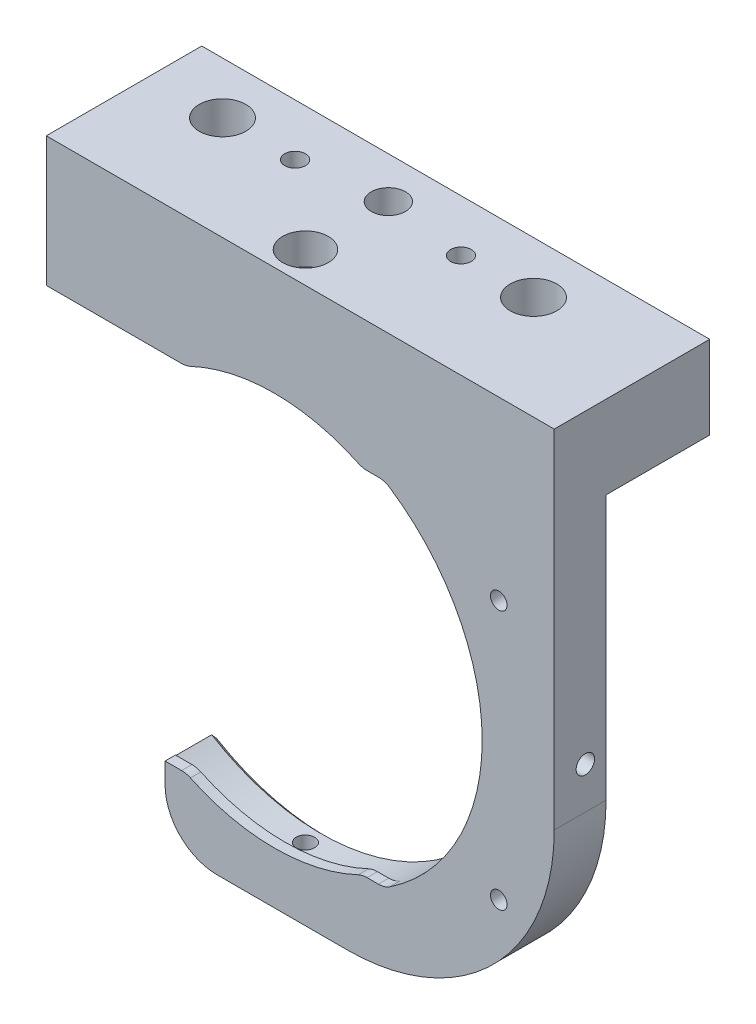
SolidWorks part; units mm, degrees
material "6061 合金"
ref_plane "前视基准面" through (0, 0, 0) normal (0, 0, 1) x (1, 0, 0)
ref_plane "上视基准面" through (0, 0, 0) normal (0, 1, 0) x (1, 0, 0)
ref_plane "右视基准面" through (0, 0, 0) normal (1, 0, 0) x (0, 0, -1)
sketch "草图2" plane through (0, 0, 0) normal (0, 0, 1) x (1, 0, 0)
  circle A0 centre (0, 0) radius 22
extrude "凸台-拉伸1" add sketch "草图2" along normal blind 5
sketch "草图4" plane through (0, 0, 0) normal (0, 0, -1) x (-1, 0, 0)
  line L0 (0, 22) -> (0, -22) construction
  line L1 (-23.9655, 0) -> (23.9655, 0) construction
  circle A0 centre (0, 0) radius 22 construction
  circle A1 centre (0, 0) radius 5.1407
  point P10 (0, 0)
sketch "草图5" plane through (0, 0, 5) normal (0, 0, 1) x (1, 0, 0)
  line L5 (-3.5, 29.5) -> (3.5, 29.5)
  line L6 (-3.5, 29.5) -> (-3.5, 14.5)
  line L13 (-3.5, 14.5) -> (3.5, 14.5)
  line L14 (3.5, 29.5) -> (3.5, 14.5)
  line L15 (-3.5, 29.5) -> (3.5, 14.5) construction
  line L16 (-3.5, 14.5) -> (3.5, 29.5) construction
  point P1 (0, 22)
  dimension "D1" = 15
  dimension "D2" = 7
extrude "凸台-拉伸2" add sketch "草图5" against normal up to surface (5 mm away) up to face at (22, 0, 0)
ref_plane "基准面4" through (-22, 0, 0) normal (-1, 0, 0) x (0, 0, 1)
sketch "草图3" plane through (0, 0, 5) normal (0, 0, 1) x (1, 0, 0)
  circle A0 centre (0, 0) radius 20.05
extrude "切除-拉伸1" [suppressed] cut sketch "草图3" against normal blind 4
sketch "草图6" plane through (-22, 0, 0) normal (-1, 0, 0) x (0, 0, 1)
  line L0 (5, -0.1401) -> (2, -0.1401) construction
  line L1 (5, -22) -> (5, 21.7198) construction
  dimension "D1" = 3
sketch "草图10" plane through (0, 29.5, 0) normal (0, 1, 0) x (1, 0, 0)
  line L0 (-3.5, -2) -> (3.5, -2) construction
  line L1 (-3.5, -5) -> (-3.5, 0) construction
  line L2 (3.5, 0) -> (3.5, -5) construction
  line L3 (0, -2) -> (0, -5) construction
  dimension "D1" = 3
hole_wizard "#2-56 螺纹孔3" positions "3D草图4" profile "草图12" tap size "#2-56" standard "ANSI Inch"
sketch3d "3D草图4"
  point P0 (0, 29.5, 2)
cosmetic thread "孔螺蚊线2" parameters "D1"=4.37, "D2"=2.1844
sketch "草图12" plane through (0, 29.5, 2) normal (1, 0, 0) x (0, 0, 1)
  line L0 (0, 0) -> (0, 15.5342)
  line L1 (0, 15.5342) -> (0.889, 15)
  line L2 (0.889, 15) -> (0.889, 0)
  line L5 (0.889, 0) -> (0, 0)
  line L10 (0, 15.5342) -> (-0.889, 15) construction
  line L11 (0, -6.35) -> (0, 107.95) construction
  dimension "螺纹孔钻头直径" = 1.778
  dimension "螺纹孔钻头深度" = 15
  dimension "导头角度" = 118
sketch "草图13" plane through (0, 0, 0) normal (0, 0, -1) x (-1, 0, 0)
  circle A0 centre (0, 0) radius 20.05
extrude "切除-拉伸2" cut sketch "草图13" against normal offset from surface (4 mm away) 1 up to face at (0, 14.68, 5)
sketch "草图14" plane through (0, 0, 4) normal (0, 0, -1) x (-1, 0, 0)
  circle A0 centre (0, 0) radius 19
extrude "切除-拉伸3" cut sketch "草图14" against normal blind 2
sketch "草图15" plane through (0, 0, 4) normal (0, 0, -1) x (-1, 0, 0)
  line L0 (-10.6303, 17) -> (10.6303, 17)
  line L1 (-10.6303, -17) -> (10.6303, -17)
  line L3 (-23.9655, 0) -> (23.9655, 0) construction
  circle A0 centre (0, 0) radius 20.05 construction
  arc A1 (-10.6303, 17) -> (-10.6303, -17) centre (0, 0) ccw
  arc A2 (10.6303, -17) -> (10.6303, 17) centre (0, 0) ccw
  dimension "D1" = 17
  dimension "D2" = 17
extrude "切除-拉伸4" cut sketch "草图15" against normal through all
sketch "草图16" plane through (0, 29.5, 0) normal (0, 1, 0) x (1, 0, 0)
  line L0 (-22, -5) -> (-22, -2) construction
  line L1 (-3.5, 0) -> (-22, 0)
  line L2 (-3.5, 0) -> (-3.5, -5)
  line L3 (-3.5, -5) -> (-22, -5)
  line L4 (-22, 0) -> (-22, -5)
  line L6 (3.5, 0) -> (22, 0)
  line L7 (3.5, 0) -> (3.5, -5)
  line L8 (3.5, -5) -> (22, -5)
  line L9 (22, 0) -> (22, -5)
extrude "凸台-拉伸3" add sketch "草图16" against normal up to surface (7.7802 mm away) up to face at (0, -0.1401, 2.5)
hole_wizard "M2 螺纹孔6" [suppressed] positions "3D草图9" profile "草图21" tap size "M2" standard "GB"
sketch3d "3D草图9"
  point P0 (-21.9996, -0.1401, 2)
sketch "草图21" plane through (-21.9996, -0.1401, 2) normal (0, 0, 1) x (0.0064, -1, 0)
  line L0 (0, 0) -> (0, 44.1874)
  line L1 (0, 44.1874) -> (0.8, 44.1874)
  line L2 (0.8, 44.1874) -> (0.8, 0)
  line L5 (0.8, 0) -> (0, 0)
  line L11 (0, -6.35) -> (0, 107.95) construction
  dimension "通孔螺纹孔钻头直径" = 1.6
  dimension "通孔螺纹孔钻头深度" = 44.1874
cosmetic thread "孔螺蚊线7" [suppressed] parameters "D2"=2
sketch "草图22" plane through (0, 29.5, 0) normal (0, 1, 0) x (1, 0, 0)
  line L0 (22, -2.5) -> (-22, -2.5) construction
  line L1 (22, -5) -> (22, 0) construction
  line L2 (-22, -5) -> (-22, -2) construction
  line L3 (0, -2.5) -> (0, -5) construction
sketch "草图23" plane through (0, 29.5, 0) normal (0, 1, 0) x (1, 0, 0)
  line L0 (22, -2.5) -> (17, -2.5) construction
  line L1 (22, -2.5) -> (-22, -2.5) construction
  line L2 (17, -2.5) -> (12, -2.5) construction
  dimension "D1" = 5
  dimension "D2" = 5
hole_wizard "大小mm 暗销孔1" [suppressed] positions "3D草图10" profile "草图24" hole size "Ø2.0" standard "GB"
sketch3d "3D草图10"
  point P0 (12, 29.5, 2.5)
sketch "草图24" plane through (12, 29.5, 2.5) normal (1, 0, 0) x (0, 0, 1)
  line L0 (0, 0) -> (0, 5.6009)
  line L1 (0, 5.6009) -> (1, 5)
  line L2 (1, 5) -> (1, 0)
  line L5 (1, 0) -> (0, 0)
  line L10 (0, 5.6009) -> (-1, 5) construction
  line L11 (0, -6.35) -> (0, 107.95) construction
  dimension "孔直径" = 2
  dimension "孔深度" = 5
  dimension "导头角度" = 118
hole_wizard "M4 螺纹孔1" [suppressed] positions "3D草图11" profile "草图25" tap size "M4" standard "GB"
sketch3d "3D草图11"
  point P0 (17, 29.5, 2.5)
sketch "草图25" plane through (17, 29.5, 2.5) normal (1, 0, 0) x (0, 0, 1)
  line L0 (0, 0) -> (0, 11.0914)
  line L1 (0, 11.0914) -> (1.65, 10.1)
  line L2 (1.65, 10.1) -> (1.65, 0)
  line L5 (1.65, 0) -> (0, 0)
  line L10 (0, 11.0914) -> (-1.65, 10.1) construction
  line L11 (0, -6.35) -> (0, 107.95) construction
  dimension "螺纹孔钻头直径" = 3.3
  dimension "螺纹孔钻头深度" = 10.1
  dimension "导头角度" = 118
cosmetic thread "孔螺蚊线8" [suppressed] parameters "D1"=8, "D2"=4
ref_plane "基准面6" through (0, 0, 0) normal (-1, 0, 0) x (0, 0, 1)
fillet "圆角1" radius 2 6 edges at (8.4853, 17, 4.5) (-8.4853, 17, 4.5) (10.6303, 17, 4.5) (-8.4853, -17, 4.5) (8.4853, -17, 4.5) (10.6303, -17, 4.5)
chamfer "倒角1" distance 0.5 angle 45 1 edges at (-20.05, 0, 0)
sketch "草图26" plane through (0, 0, 5) normal (0, 0, 1) x (1, 0, 0)
  line L0 (-10.6303, 17) -> (-8.9443, 17) construction
  line L1 (-22, 17) -> (-10.54, 17)
  line L2 (-22, 17) -> (-22, -21.4907)
  line L3 (-22, -21.4907) -> (-10.54, -21.4907)
  line L4 (-10.54, 17) -> (-10.54, -21.4907)
  dimension "D1" = 11.46
extrude "切除-拉伸5" cut sketch "草图26" against normal through all
fillet "圆角6" [suppressed] radius 1.5
sketch "草图27" plane through (0, 0, 0) normal (0, 0, -1) x (-1, 0, 0)
  line L0 (-22, 0) -> (-22, 29.5) construction
  line L1 (22, 29.5) -> (-22, 29.5)
  line L2 (22, 29.5) -> (22, 21.5)
  line L3 (22, 21.5) -> (-22, 21.5)
  line L4 (-22, 29.5) -> (-22, 21.5)
  dimension "D1" = 8
extrude "凸台-拉伸4" add sketch "草图27" along normal blind 10
sketch "草图28" plane through (0, 21.5, 0) normal (0, -1, 0) x (-1, 0, 0)
  line L0 (22, 5) -> (15, 5) construction
  line L1 (22, 10) -> (22, 0) construction
  line L2 (15, 5) -> (10, 5) construction
  line L3 (-15, 5) -> (-22, 5) construction
  line L4 (-10, 5) -> (-15, 5) construction
  line L5 (-22, 10) -> (-22, 0) construction
  dimension "D1" = 7
  dimension "D2" = 5
hole_wizard "打孔尺寸(%根据)内六角圆柱头螺钉的类型2" positions "3D草图13" profile "草图30" counterbore size "M4" standard "GB"
sketch3d "3D草图13"
  point P0 (-15, 21.5, -5)
  point P3 (15, 21.5, -5)
sketch "草图30" plane through (-15, 21.5, -5) normal (1, 0, 0) x (0, 0, -1)
  line L0 (0, 0) -> (0, 11.4519)
  line L1 (0, 11.4519) -> (2.25, 10.1)
  line L2 (2.25, 10.1) -> (2.25, 4.6)
  line L3 (2.25, 4.6) -> (4, 4.6)
  line L4 (4, 4.6) -> (4, 0)
  line L5 (4, 0) -> (0, 0)
  line L10 (0, 11.4519) -> (-2.25, 10.1) construction
  line L11 (0, -6.35) -> (0, 107.95) construction
  dimension "孔直径" = 4.5
  dimension "孔深度" = 10.1
  dimension "柱形沉头孔直径" = 8
  dimension "柱形沉头孔深度" = 4.6
  dimension "导头角度" = 118
sketch "草图31" plane through (22, 0, 0) normal (1, 0, 0) x (0, 0, -1)
  line L6 (-5, 0) -> (0, 0)
  line L7 (0, 0) -> (0, 21.5)
  line L8 (0, 21.5) -> (10, 21.5)
  line L9 (10, 21.5) -> (10, 29.5)
  line L10 (10, 29.5) -> (-5, 29.5)
  line L11 (-5, 29.5) -> (-5, 0)
  line L12 (-5, 0) -> (0, 0)
  line L13 (0, 0) -> (0, 21.5)
  line L14 (0, 21.5) -> (10, 21.5)
  line L15 (10, 21.5) -> (10, 29.5)
  line L16 (10, 29.5) -> (-5, 29.5)
  line L17 (-5, 29.5) -> (-5, 0)
  dimension "D1" = 0
extrude "凸台-拉伸5" add sketch "草图31" along normal blind 5
sketch "草图32" plane through (27, 0, 0) normal (1, 0, 0) x (0, 0, -1)
  line L1 (0, 0) -> (-5, 0)
  line L2 (0, 0) -> (0, -22)
  line L3 (0, -22) -> (-5, -22)
  line L4 (-5, 0) -> (-5, -22)
extrude "凸台-拉伸6" add sketch "草图32" against normal up to surface (5 mm away) up to face at (8.4788, -14.2874, 2.5)
sketch "草图33" [suppressed] plane through (0, 29.5, 0) normal (0, 1, 0) x (1, 0, 0)
  line L0 (-15, 5) -> (-15, -2) construction
  line L1 (15, 5) -> (15, -2) construction
  dimension "D1" = 7
hole_wizard "大小mm 暗销孔2" [suppressed] positions "3D草图14" profile "草图34" hole size "Ø4.0" standard "GB"
sketch3d "3D草图14" [suppressed]
  point P0 (-15, 29.5, 2)
  point P3 (15, 29.5, 2)
sketch "草图34" plane through (-15, 29.5, 2) normal (1, 0, 0) x (0, 0, 1)
  line L0 (0, 0) -> (0, 6.2017)
  line L1 (0, 6.2017) -> (2, 5)
  line L2 (2, 5) -> (2, 0)
  line L5 (2, 0) -> (0, 0)
  line L10 (0, 6.2017) -> (-2, 5) construction
  line L11 (0, -6.35) -> (0, 107.95) construction
  dimension "孔直径" = 4
  dimension "孔深度" = 5
  dimension "导头角度" = 118
sketch "草图36" plane through (0, 29.5, 0) normal (0, 1, 0) x (1, 0, 0)
  line L0 (-15, 5) -> (-8, 5) construction
  line L1 (15, 5) -> (8, 5) construction
  dimension "D1" = 7
  dimension "D2" = 7
hole_wizard "大小mm 暗销孔4" positions "3D草图16" profile "草图37" hole size "Ø2.0" standard "GB"
sketch3d "3D草图16"
  point P0 (-8, 29.5, -5)
  point P3 (8, 29.5, -5)
sketch "草图37" plane through (-8, 29.5, -5) normal (1, 0, 0) x (0, 0, 1)
  line L0 (0, 0) -> (0, 4.6009)
  line L1 (0, 4.6009) -> (1, 4)
  line L2 (1, 4) -> (1, 0)
  line L5 (1, 0) -> (0, 0)
  line L10 (0, 4.6009) -> (-1, 4) construction
  line L11 (0, -6.35) -> (0, 107.95) construction
  dimension "孔直径" = 2
  dimension "孔深度" = 4
  dimension "导头角度" = 118
sketch "草图38" plane through (0, 29.5, 0) normal (0, 1, 0) x (1, 0, 0)
  line L0 (-8, 5) -> (0, 5) construction
  line L1 (0, 8.25) -> (0, -8.25) construction
hole_wizard "打孔尺寸(%根据)内六角圆柱头螺钉的类型3" [suppressed] positions "3D草图17" profile "草图39" counterbore size "M4" standard "GB"
sketch3d "3D草图17"
  point P0 (0, 29.5, -5)
sketch "草图39" plane through (0, 29.5, -5) normal (1, 0, 0) x (0, 0, 1)
  line L0 (0, 0) -> (0, 51.5)
  line L1 (0, 51.5) -> (2.4, 51.5)
  line L3 (2.4, 51.5) -> (2.4, 6)
  line L4 (2.4, 6) -> (4, 6)
  line L5 (4, 6) -> (4, 0)
  line L7 (4, 0) -> (0, 0)
  line L11 (0, -6.35) -> (0, 107.95) construction
  dimension "通孔孔直径" = 4.8
  dimension "通孔孔深度" = 51.5
  dimension "柱形沉头孔直径" = 8
  dimension "柱形沉头孔深度" = 6
sketch "草图41" plane through (0, 29.5, 0) normal (0, 1, 0) x (1, 0, 0)
  circle A0 centre (0, -2) radius 2.2
extrude "切除-拉伸6" cut sketch "草图41" against normal blind 3
sketch "草图45" plane through (0, -22, 0) normal (0, -1, 0) x (1, 0, 0)
  line L4 (0, 5) -> (0, 0)
  line L5 (0, 0) -> (27, 0)
  line L6 (27, 0) -> (27, 5)
  line L7 (27, 5) -> (0, 5)
  line L8 (0, 5) -> (0, 0)
  line L9 (0, 0) -> (27, 0)
  line L10 (27, 0) -> (27, 5)
  line L11 (27, 5) -> (0, 5)
  dimension "D1" = 0
extrude "凸台-拉伸7" add sketch "草图45" along normal blind 2
sketch "草图47" plane through (0, -24, 0) normal (0, -1, 0) x (1, 0, 0)
  line L1 (-10.54, 5) -> (0, 5)
  line L2 (-10.54, 5) -> (-10.54, 0)
  line L3 (-10.54, 0) -> (0, 0)
  line L4 (0, 5) -> (0, 0)
extrude "凸台-拉伸9" add sketch "草图47" against normal up to surface (2 mm away) up to face at (-5.3544, -20.9863, 2.5)
sketch "草图50" plane through (0, -24, 0) normal (0, -1, 0) x (1, 0, 0)
  line L0 (0, 2) -> (0, 0) construction
hole_wizard "#2-56 螺纹孔1" positions "3D草图22" profile "草图51" tap size "#2-56" standard "ANSI Inch"
sketch3d "3D草图22"
  point P0 (0, -24, 2)
sketch "草图51" plane through (0, -24, 2) normal (1, 0, 0) x (0, 0, -1)
  line L0 (0, 0) -> (0, 6.2642)
  line L1 (0, 6.2642) -> (0.889, 5.73)
  line L2 (0.889, 5.73) -> (0.889, 0)
  line L5 (0.889, 0) -> (0, 0)
  line L10 (0, 6.2642) -> (-0.889, 5.73) construction
  line L11 (0, -6.35) -> (0, 107.95) construction
  dimension "螺纹孔钻头直径" = 1.778
  dimension "螺纹孔钻头深度" = 5.73
  dimension "导头角度" = 118
cosmetic thread "孔螺蚊线10" parameters "D1"=3.9697, "D2"=2.1844
fillet "圆角7" radius 20 1 edges at (27, -24, 2.5)
fillet "圆角8" radius 5 1 edges at (-10.54, -24, 2.5)
ref_plane "基准面7" through (0, 0, 0) normal (0, 1, 0) x (-1, 0, 0)
sketch "草图53" plane through (27, 0, 0) normal (1, 0, 0) x (0, 0, -1)
  line L0 (-5, 0) -> (-2, 0) construction
  line L1 (28.031, 0) -> (-28.031, 0) construction
  line L2 (-5, 29.5) -> (-5, -4) construction
  point P7 (0, 0)
  dimension "D1" = 3
hole_wizard "#2-56 螺纹孔2" positions "3D草图23" profile "草图54" tap size "#2-56" standard "ANSI Inch" end condition through all
sketch3d "3D草图23"
  point P0 (27, 0, 2)
cosmetic thread "孔螺蚊线11" parameters "D2"=2.1844
sketch "草图54" plane through (27, 0, 2) normal (0, 1, 0) x (0, 0, -1)
  line L0 (0, 0) -> (0, 49)
  line L1 (0, 49) -> (0.889, 49)
  line L2 (0.889, 49) -> (0.889, 0)
  line L5 (0.889, 0) -> (0, 0)
  line L11 (0, -6.35) -> (0, 107.95) construction
  dimension "通孔螺纹孔钻头直径" = 1.778
  dimension "通孔螺纹孔钻头深度" = 49
sketch "草图55" plane through (0, 21.5, 0) normal (0, -1, 0) x (-1, 0, 0)
  line L0 (0, 0) -> (0, 6) construction
  line L1 (0, -8.25) -> (0, 8.25) construction
  dimension "D1" = 6
hole_wizard "M4 螺纹孔2" positions "3D草图24" profile "草图57" tap size "M4" standard "GB" end condition through all
sketch3d "3D草图24"
  point P0 (0, 21.5, -6)
sketch "草图57" plane through (0, 21.5, -6) normal (1, 0, 0) x (0, 0, -1)
  line L0 (0, 0) -> (0, 8)
  line L1 (0, 8) -> (1.65, 8)
  line L2 (1.65, 8) -> (1.65, 0)
  line L5 (1.65, 0) -> (0, 0)
  line L11 (0, -6.35) -> (0, 107.95) construction
  dimension "通孔螺纹孔钻头直径" = 3.3
  dimension "通孔螺纹孔钻头深度" = 8
cosmetic thread "孔螺蚊线13" parameters "D2"=4
sketch "草图58" plane through (0, 0, 0) normal (0, 0, -1) x (-1, 0, 0)
  line L0 (0, 0) -> (-21.6506, -12.5) construction
  line L1 (0, 0) -> (-21.6506, 12.5) construction
  line L3 (-23.9655, 0) -> (23.9655, 0) construction
  circle A0 centre (0, 0) radius 25 construction
  dimension "D1" = 30
  dimension "D2" = 60
hole_wizard "M2 螺纹孔10" positions "3D草图25" profile "草图59" tap size "M2" standard "GB" end condition through all
sketch3d "3D草图25"
  point P0 (21.6506, 12.5, 0)
  point P3 (21.6506, -12.5, 0)
sketch "草图59" plane through (21.6506, 12.5, 0) normal (1, 0, 0) x (0, 1, 0)
  line L0 (0, 0) -> (0, 5)
  line L1 (0, 5) -> (0.8, 5)
  line L2 (0.8, 5) -> (0.8, 0)
  line L5 (0.8, 0) -> (0, 0)
  line L11 (0, -6.35) -> (0, 107.95) construction
  dimension "通孔螺纹孔钻头直径" = 1.6
  dimension "通孔螺纹孔钻头深度" = 5
cosmetic thread "孔螺蚊线14" parameters "D1"=4, "D2"=2.6
cosmetic thread "孔螺蚊线15" parameters "D1"=4, "D2"=2.6
